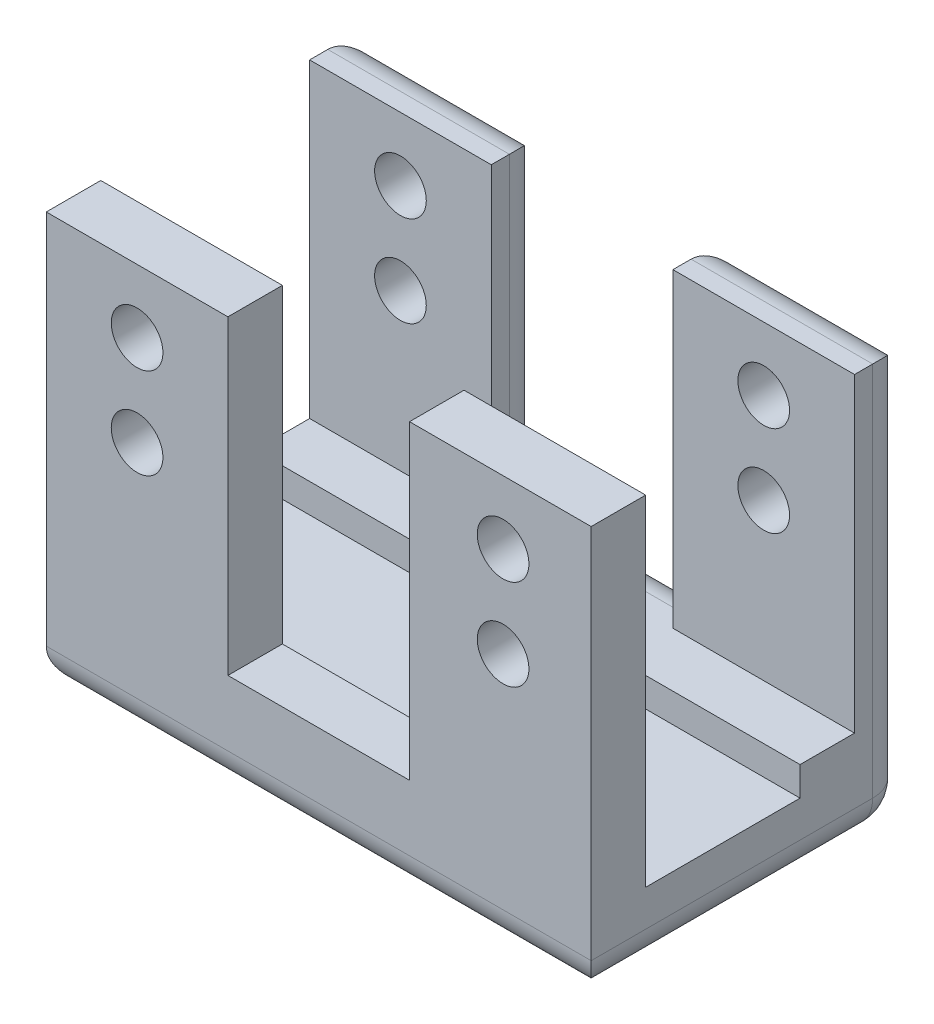
SolidWorks part; units mm, degrees
ref_plane "Front Plane" through (0, 0, 0) normal (0, 0, 1) x (1, 0, 0)
ref_plane "Top Plane" through (0, 0, 0) normal (0, 1, 0) x (1, 0, 0)
ref_plane "Right Plane" through (0, 0, 0) normal (1, 0, 0) x (0, 0, -1)
sketch "Sketch1" plane through (0, 0, 0) normal (0, 1, 0) x (1, 0, 0)
  line L1 (0, 0) -> (30, 0)
  line L2 (0, 0) -> (0, 17.5)
  line L3 (0, 17.5) -> (30, 17.5)
  line L4 (30, 0) -> (30, 17.5)
  dimension "D1" = 30
  dimension "D2" = 17.5
extrude "Boss-Extrude1" add sketch "Sketch1" along normal blind 4
sketch "Sketch2" plane through (0, 4, 0) normal (0, 1, 0) x (1, 0, 0)
  line L0 (30, 0) -> (30, 17.5) construction
  line L1 (0, 17.5) -> (30, 17.5)
  line L2 (0, 17.5) -> (0, 11.5)
  line L3 (0, 11.5) -> (30, 11.5)
  line L4 (30, 17.5) -> (30, 11.5)
  dimension "D1" = 6
extrude "Boss-Extrude2" add sketch "Sketch2" along normal blind 1.601
sketch "Sketch3" plane through (0, 4, 0) normal (0, 1, 0) x (1, 0, 0)
  line L1 (0, 0) -> (10, 0)
  line L2 (0, 0) -> (0, 3)
  line L3 (0, 3) -> (10, 3)
  line L4 (10, 0) -> (10, 3)
  line L5 (30, 0) -> (20, 0)
  line L6 (30, 0) -> (30, 3)
  line L7 (30, 3) -> (20, 3)
  line L8 (20, 0) -> (20, 3)
  dimension "D1" = 10
  dimension "D2" = 3
extrude "Boss-Extrude3" add sketch "Sketch3" along normal blind 18.7
sketch "Sketch4" plane through (0, 5.601, 0) normal (0, 1, 0) x (1, 0, 0)
  line L1 (0, 17.5) -> (10, 17.5)
  line L2 (0, 17.5) -> (0, 14.5)
  line L3 (0, 14.5) -> (10, 14.5)
  line L4 (10, 17.5) -> (10, 14.5)
  line L5 (30, 17.5) -> (20, 17.5)
  line L6 (30, 17.5) -> (30, 14.5)
  line L7 (30, 14.5) -> (20, 14.5)
  line L8 (20, 17.5) -> (20, 14.5)
  dimension "D1" = 10
  dimension "D2" = 3
extrude "Boss-Extrude4" add sketch "Sketch4" along normal blind 17.099
sketch "Sketch5" plane through (0, 4, 0) normal (0, 1, 0) x (1, 0, 0)
  line L1 (10, 3) -> (20, 3)
  line L2 (10, 3) -> (10, 0)
  line L3 (10, 0) -> (20, 0)
  line L4 (20, 3) -> (20, 0)
extrude "Boss-Extrude5" add sketch "Sketch5" along normal blind 1.601
fillet "Fillet1" radius 2 11 edges at (30, 11.35, -17.5) (25, 22.7, -17.5) (20, 14.1505, -17.5) (15, 5.601, -17.5) (10, 14.1505, -17.5) (5, 22.7, -17.5) (0, 11.35, -17.5) (15, 0, 0) (30, 0, -8.75) (15, 0, -17.5) (0, 0, -8.75)
sketch "Sketch6" plane through (0, 0, -14.5) normal (0, 0, 1) x (1, 0, 0)
  line L0 (0, 22.7) -> (10, 22.7) construction
  line L1 (10, 22.7) -> (20, 22.7) construction
  line L2 (15, 22.7) -> (15, 17.0758) construction
  line L3 (5, 22.7) -> (5, 19.2) construction
  circle A0 centre (5, 19.2) radius 1.4224
  circle A1 centre (25, 19.2) radius 1.4224
  circle A2 centre (5, 14.2) radius 1.4224
  circle A3 centre (25, 14.2) radius 1.4224
  dimension "D1" = 2.8448
  dimension "D2" = 3.5
  dimension "D3" = 2
extrude "Cut-Extrude1" cut sketch "Sketch6" against normal up to next
sketch "Sketch7" plane through (0, 0, -3) normal (0, 0, -1) x (-1, 0, 0)
  line L0 (0, 22.7) -> (-10, 22.7) construction
  line L1 (-10, 22.7) -> (-20, 22.7) construction
  line L2 (-15.0754, 22.7) -> (-15.0754, 19.6857) construction
  line L3 (-5, 22.7) -> (-5, 19.2) construction
  circle A0 centre (-5, 19.2) radius 1.4224
  circle A1 centre (-25.1507, 19.2) radius 1.4224
  circle A2 centre (-25.1507, 14.2) radius 1.4224
  circle A3 centre (-5, 14.2) radius 1.4224
  dimension "D1" = 2.8448
  dimension "D2" = 3.5
  dimension "D3" = 2
extrude "Cut-Extrude2" cut sketch "Sketch7" against normal up to next
